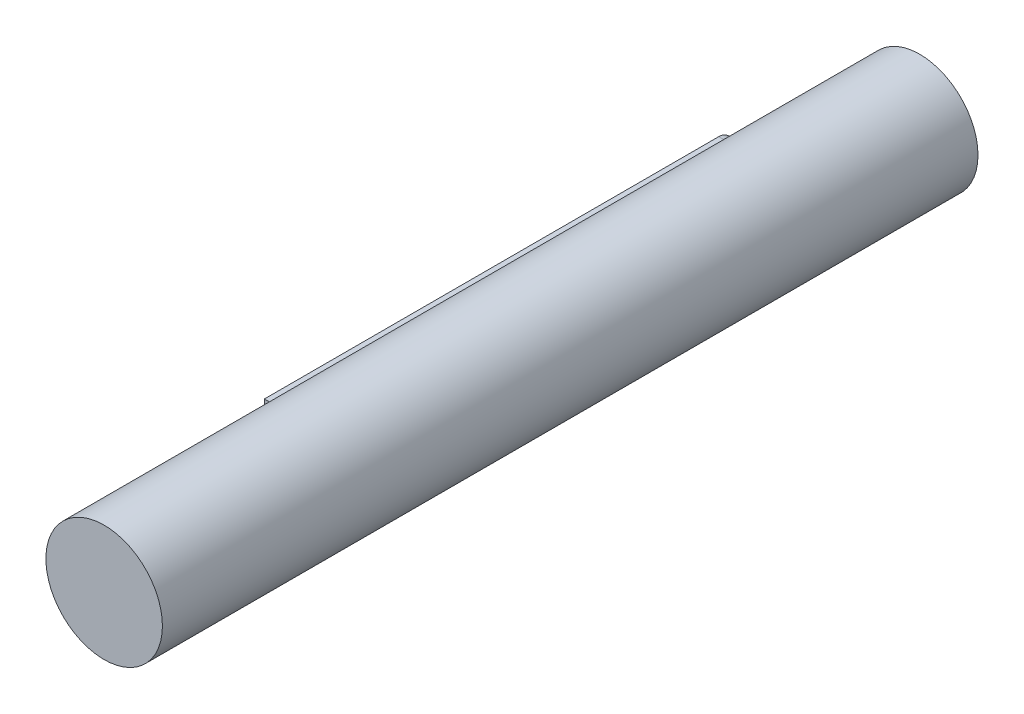
SolidWorks part; units mm, degrees
ref_plane "Front Plane" through (0, 0, 0) normal (1, 0, 0) x (0, 1, 0)
ref_plane "Top Plane" through (0, 0, 0) normal (0, 0, 1) x (0, 1, 0)
ref_plane "Right Plane" through (0, 0, 0) normal (0, 1, 0) x (-1, 0, 0)
sketch "Sketch1" plane through (0, 0, 0) normal (0, 0, 1) x (0, 1, 0)
  line L1 (-2.5, 12.5) -> (2.5, 12.5)
  line L2 (-2.5, 12.5) -> (-2.5, 9.6825)
  line L4 (2.5, 12.5) -> (2.5, 9.6825)
  arc A0 (-2.5, 9.6825) -> (2.5, 9.6825) centre (0, 0) ccw
  point P3 (0, 10)
  dimension "D1" = 20
  dimension "D2" = 5
extrude "Boss-Extrude1" add sketch "Sketch1" along normal blind 140
sketch "Sketch2" plane through (0, 0, 0) normal (0, 0, -1) x (1, 0, 0)
  line L1 (-9.6825, 2.5) -> (-12.5, 2.5)
  line L3 (-9.6825, -2.5) -> (-12.5, -2.5)
  line L4 (-12.5, 2.5) -> (-12.5, -2.5)
  arc A0 (-9.6825, 2.5) -> (-9.6825, -2.5) centre (0, 0) ccw
  point P4 (-10, 0)
extrude "Cut-Extrude1" cut sketch "Sketch2" against normal blind 20
sketch "Sketch3" plane through (0, 0, 140) normal (0, 0, 1) x (1, 0, 0)
  line L0 (-12.5, -2.5) -> (-9.6825, -2.5) construction
  line L1 (-9.6825, 2.5) -> (-12.5, 2.5)
  line L3 (-9.6825, -2.5) -> (-12.5, -2.5)
  line L4 (-12.5, 2.5) -> (-12.5, -2.5)
  line L7 (-12.5, 2.5) -> (-12.5, -2.5) construction
  arc A0 (-9.6825, 2.5) -> (-9.6825, -2.5) centre (0, 0) ccw
  point P4 (-10, 0)
extrude "Cut-Extrude2" cut sketch "Sketch3" against normal blind 40
sketch "Sketch4" plane through (0, 0, 20) normal (0, 0, -1) x (1, 0, 0)
  line L0 (-9.6825, 2.5) -> (-12.5, 2.5)
  line L1 (-12.5, 2.5) -> (-12.5, -2.5)
  line L2 (-12.5, -2.5) -> (-9.6825, -2.5)
  arc A0 (-9.6825, 2.5) -> (-9.6825, -2.5) centre (0, 0) ccw
extrude "Cut-Extrude4" cut sketch "Sketch4" against normal blind 0.0001
fillet "Fillet2" radius 2 3 edges at (-11.0912, -2.5, 20.0001) (-11.0912, 2.5, 20.0001) (-12.5, 0, 20.0001) conic rho 0.5
